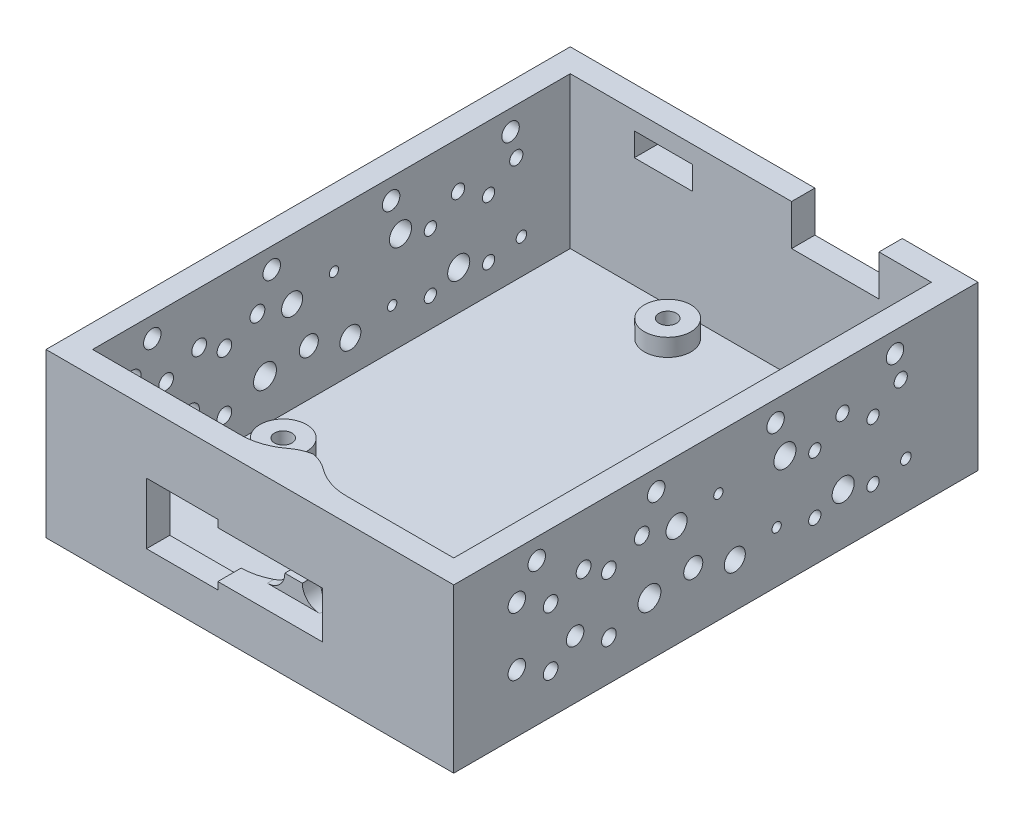
SolidWorks part; units mm, degrees
ref_plane "Front Plane" through (0, 0, 0) normal (0, 0, 1) x (1, 0, 0)
ref_plane "Top Plane" through (0, 0, 0) normal (0, 1, 0) x (1, 0, 0)
ref_plane "Right Plane" through (0, 0, 0) normal (1, 0, 0) x (0, 0, -1)
sketch "Sketch1" plane through (0, 0, 0) normal (0, 1, 0) x (1, 0, 0)
  line L1 (-35, 45) -> (35, 45)
  line L2 (-35, 45) -> (-35, -45)
  line L3 (-35, -45) -> (35, -45)
  line L4 (35, 45) -> (35, -45)
  line L5 (-35, 45) -> (35, -45) construction
  line L6 (-35, -45) -> (35, 45) construction
  point P0 (0, 0)
  dimension "D1" = 70
  dimension "D2" = 90
extrude "Boss-Extrude1" add sketch "Sketch1" along normal blind 30
shell "Shell1" thickness 4
sketch "Sketch2" plane through (0, 0, 45) normal (0, 0, 1) x (1, 0, 0)
  line L0 (-35, 0) -> (35, 0) construction
  line L2 (-35, 30) -> (-35, 0) construction
  line L3 (-17.75, 19.5) -> (-17.75, 9)
  line L4 (-17.75, 9) -> (-5.5, 9)
  line L5 (-5.5, 9) -> (-5.5, 19.5)
  line L6 (-5.5, 19.5) -> (-17.75, 19.5)
  line L8 (-17.25, 19) -> (-17.25, 9.5)
  line L9 (-17.25, 9.5) -> (-6, 9.5)
  line L10 (-6, 9.5) -> (-6, 19)
  line L11 (-6, 19) -> (-17.25, 19)
  dimension "D3" = 11.25
  dimension "D1" = 9.5
  dimension "D4" = 17.75
  dimension "D5" = 9.5
  dimension "D2" = 0.5
extrude "Cut-Extrude1" cut sketch "Sketch2" against normal blind 7
sketch "Sketch3" plane through (0, 0, 45) normal (0, 0, 1) x (1, 0, 0)
  line L0 (-5.5, 14.25) -> (35, 14.25) construction
  line L2 (35, 30) -> (35, 0) construction
  line L3 (-5.5, 9) -> (-5.5, 19.5) construction
  line L4 (-5.5, 18.25) -> (12.5, 18.25)
  line L5 (-5.5, 18.25) -> (-5.5, 10.25)
  line L6 (-5.5, 10.25) -> (12.5, 10.25)
  line L7 (12.5, 18.25) -> (12.5, 10.25)
  line L8 (-5.5, 18.25) -> (12.5, 10.25) construction
  line L9 (-5.5, 10.25) -> (12.5, 18.25) construction
  point P6 (3.5, 14.25)
  dimension "D2" = 8
  dimension "D3" = 18
extrude "Cut-Extrude2" cut sketch "Sketch3" against normal blind 7
sketch "Sketch4" plane through (0, 0, -45) normal (0, 0, -1) x (-1, 0, 0)
  line L0 (-34.9139, 29.5469) -> (35, 32) construction
  line L1 (-22, 30) -> (-7, 30)
  line L2 (-22, 30) -> (-22, 23)
  line L3 (-22, 23) -> (-7, 23)
  line L4 (-7, 30) -> (-7, 23)
  line L5 (-35, 30) -> (-35, 0) construction
  line L6 (-35, 30) -> (35, 30) construction
  dimension "D1" = 13
  dimension "D2" = 7
  dimension "D3" = 15
extrude "Cut-Extrude3" cut sketch "Sketch4" against normal blind 7
sketch "Sketch6" plane through (0, 0, -1.7195) normal (0, -1, 0) x (1, 0, 0)
  line L0 (35, -43.2805) -> (-35, -43.2805) construction
  circle A4 centre (18.6259, -34.2805) radius 1.5
  circle A5 centre (-9.2741, -34.2805) radius 1.5
  circle A6 centre (23.7259, 17.8195) radius 1.5
  circle A7 centre (-24.4741, 16.5195) radius 1.5
  circle A8 centre (-24.4741, 16.5195) radius 4
  circle A9 centre (23.7259, 17.8195) radius 4
  circle A10 centre (-9.2741, -34.2805) radius 4
  circle A11 centre (18.6259, -34.2805) radius 4
  dimension "D1" = 27.9
  dimension "D2" = 5.1
  dimension "D3" = 52.1
  dimension "D4" = 15.2
  dimension "D5" = 50.8
  dimension "D6" = 9
extrude "Boss-Extrude2" add sketch "Sketch6" against normal blind 7 contours A8 A7 | A9 A6 | A11 A4 | A10 A5
sketch "Sketch7" plane through (31, 0, 0) normal (-1, 0, 0) x (0, 0, 1)
  line L0 (0, 30) -> (0, 23) construction
  line L1 (-41, 30) -> (41, 30)
  line L2 (-41, 30) -> (-41, 23)
  line L3 (-41, 23) -> (41, 23)
  line L4 (41, 30) -> (41, 23)
  line L5 (0, 23) -> (-41, 23) construction
  line L6 (-20.5, 23) -> (-20.5, 30) construction
  line L7 (-20.5, 23) -> (-41, 30) construction
  circle A0 centre (-30.75, 26.5) radius 1.5
  circle A1 centre (-10.25, 26.5) radius 1.5
  circle A2 centre (10.25, 26.5) radius 1.5
  circle A3 centre (30.75, 26.5) radius 1.5
  dimension "D2" = 3
  dimension "D1" = 7
extrude "Cut-Extrude4" cut sketch "Sketch7" against normal through all both and the other way through all contours A0 | A1 | A2 | A3
sketch "Sketch8" plane through (0, 0, -45) normal (0, 0, -1) x (-1, 0, 0)
  line L0 (35, 30) -> (35, 0) construction
  line L1 (20, 23) -> (10, 23)
  line L2 (20, 23) -> (20, 27)
  line L3 (20, 27) -> (10, 27)
  line L4 (10, 23) -> (10, 27)
  line L5 (-7, 30) -> (35, 30) construction
  dimension "D1" = 15
  dimension "D2" = 10
  dimension "D3" = 4
  dimension "D4" = 3
extrude "Cut-Extrude5" cut sketch "Sketch8" against normal blind 7
sketch "Sketch9" plane through (0, 4, 0) normal (0, 1, 0) x (1, 0, 0)
  line L0 (12.5, -41) -> (-5.5, -41) construction
  line L1 (12.5, -41) -> (-5.5, -41)
  line L2 (2, -41) -> (2, -37.5)
  line L3 (2, -41) -> (5, -41)
  line L4 (3.5, -41) -> (3.5, -37.5)
  line L5 (2, -37.5) -> (5, -37.5)
  line L6 (5, -41) -> (5, -37.5)
  dimension "D1" = 3.5
  dimension "D2" = 1.5
extrude "Boss-Extrude3" add sketch "Sketch9" along direction (0, 1, 0) on the side of the normal up to surface (26 mm away) contours L5 L2 L1 L4 | L3 L6 L5 L4
sketch "Sketch10" plane through (0, 0, 41) normal (0, 0, 1) x (1, 0, 0)
  line L0 (2, 18.25) -> (5, 10.25) construction
  line L1 (5, 18.25) -> (5, 10.25) construction
  line L2 (2, 15.25) -> (5, 15.25)
  line L3 (2, 15.25) -> (2, 13.25)
  line L4 (2, 13.25) -> (5, 13.25)
  line L5 (5, 15.25) -> (5, 13.25)
  line L6 (2, 15.25) -> (5, 13.25) construction
  line L7 (2, 13.25) -> (5, 15.25) construction
  point P4 (3.5, 14.25)
  dimension "D1" = 2
extrude "Cut-Extrude6" cut sketch "Sketch10" against normal blind 10
fillet "Fillet1" radius 10 3 edges at (2, 24.125, 41) (5, 7.125, 41) (2, 7.125, 41)
fillet "Fillet2" radius 3 4 edges at (5, 18.25, 39.25) (2, 18.25, 39.25) (5, 10.25, 39.25) (2, 10.25, 39.25)
fillet "Fillet3" radius 7 4 edges at (2, 22.625, 37.5) (5, 22.625, 37.5) (5, 8.625, 37.5) (2, 8.625, 37.5)
chamfer "Chamfer1" distance 2 angle 45 4 edges at (0, 0, -45) (-35, 0, 0) (0, 0, 45) (35, 0, 0)
sketch "Sketch11" plane through (35, 0, 0) normal (1, 0, 0) x (0, 0, -1)
  line L0 (-45, 16) -> (45, 16) construction
  line L1 (-45, 30) -> (-45, 2) construction
  line L2 (45, 30) -> (45, 2) construction
  circle A0 centre (-34.169, 21.9936) radius 1.5
  circle A1 centre (-28.3693, 18.8672) radius 1.2542
  circle A2 centre (-22.7055, 21.1688) radius 1.2737
  circle A4 centre (-6.7489, 19.6131) radius 1.805
  circle A5 centre (0.4303, 20.8466) radius 0.7997
  circle A6 centre (11.8538, 20.7699) radius 1.8956
  circle A7 centre (16.9816, 18.9853) radius 1.0516
  circle A8 centre (21.7333, 22.1437) radius 1.1331
  circle A11 centre (-34.169, 11.9936) radius 1.5
  circle A12 centre (-28.3693, 8.8672) radius 1.2542
  circle A14 centre (-11.402, 11.2388) radius 1.9639
  circle A18 centre (16.9816, 8.9853) radius 1.0516
  circle A20 centre (32.6151, 9.9707) radius 0.9017
  circle A22 centre (-24.169, 11.9936) radius 1.5
  circle A23 centre (-18.3693, 8.8672) radius 1.2542
  circle A25 centre (-3.8837, 11.9922) radius 1.6358
  circle A26 centre (3.2511, 9.6131) radius 1.805
  circle A27 centre (10.4303, 10.8466) radius 0.7997
  circle A28 centre (21.8538, 10.7699) radius 1.8956
  circle A29 centre (26.9816, 8.9853) radius 1.0516
  circle A34 centre (-18.3693, 18.8672) radius 1.2542
  circle A35 centre (-12.7055, 21.1688) radius 1.2737
  circle A40 centre (26.9816, 18.9853) radius 1.0516
  circle A41 centre (31.7333, 22.1437) radius 1.1331
  circle A48 centre (21.7333, 12.1437) radius 1.1331 [skipped]
  circle A49 centre (10.4303, 20.8466) radius 0.7997 [skipped]
  circle A50 centre (3.2511, 19.6131) radius 1.805 [skipped]
  circle A52 centre (-6.7489, 9.6131) radius 1.805 [skipped]
  circle A53 centre (0.4303, 10.8466) radius 0.7997 [skipped]
  circle A54 centre (-12.7055, 11.1688) radius 1.2737 [skipped]
  circle A55 centre (-24.169, 21.9936) radius 1.5 [skipped]
  circle A56 centre (-22.7055, 11.1688) radius 1.2737 [skipped]
  circle A57 centre (11.8538, 10.7699) radius 1.8956 [skipped]
  circle A58 centre (21.8538, 20.7699) radius 1.8956 [skipped]
  circle A59 centre (31.7333, 12.1437) radius 1.1331 [skipped]
  dimension "D1" = 3
  dimension "D2" = 2
  dimension "D3" = 2
extrude "Cut-Extrude7" cut sketch "Sketch11" against normal through all both and the other way through all
